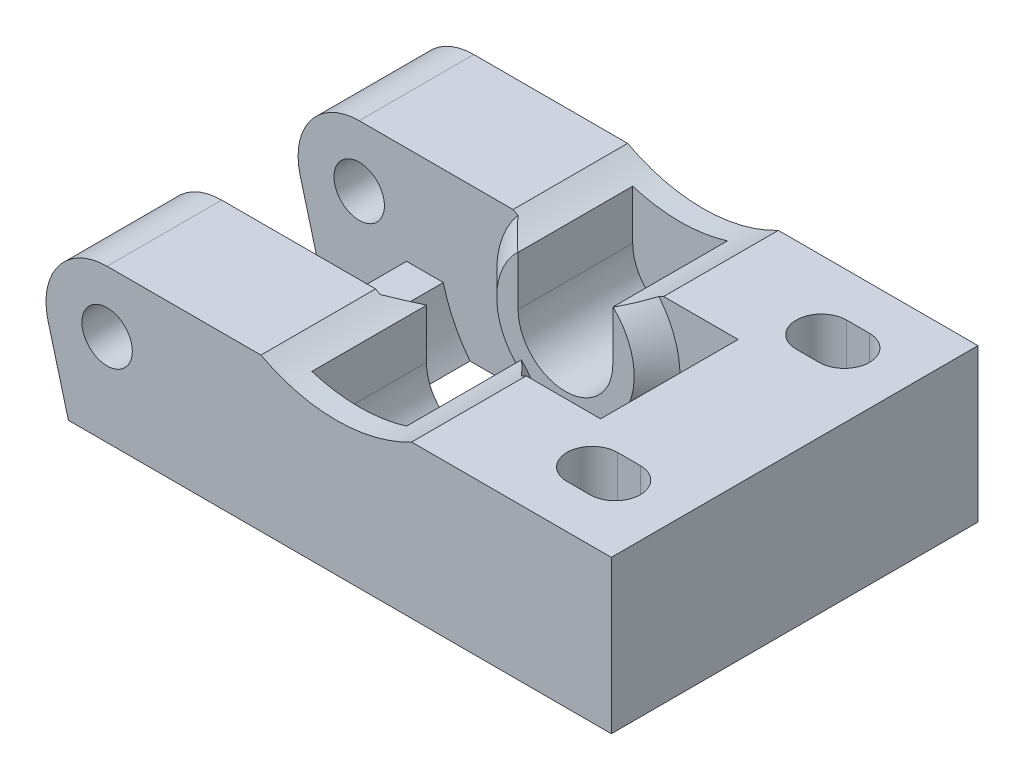
SolidWorks part; units mm, degrees
ref_plane "Front Plane" through (0, 0, 0) normal (0, 0, 1) x (1, 0, 0)
ref_plane "Top Plane" through (0, 0, 0) normal (0, 1, 0) x (1, 0, 0)
ref_plane "Right Plane" through (0, 0, 0) normal (1, 0, 0) x (0, 0, -1)
sketch "Sketch1" plane through (0, 0, 0) normal (0, 0, 1) x (1, 0, 0)
  line L0 (-18.8637, -1.0353) -> (-17.5334, -6)
  line L1 (-17.5334, -6) -> (18, -6)
  line L3 (-15, 4) -> (18, 4)
  line L4 (18, -6) -> (18, 4)
  circle A1 centre (-15, 0) radius 1.65
  arc A2 (-15, 4) -> (-18.8637, -1.0353) centre (-15, 0) ccw
  dimension "D2" = 4
  dimension "D3" = 3.3
  dimension "D4" = 4
  dimension "D1" = 15
  dimension "D5" = 10
  dimension "D6" = 105
  dimension "D7" = 18
extrude "Boss-Extrude1" add sketch "Sketch1" along normal blind 24
ref_plane "Plane1" through (0, 0, 12) normal (0, 0, 1) x (1, 0, 0)
sketch "Sketch2" plane through (0, 0, 12) normal (0, 0, 1) x (1, 0, 0)
  line L0 (-11.9012, -2.4212) -> (-19.8091, -31.934)
  line L1 (-19.8091, 9.8) -> (9.8, 9.8)
  line L2 (9.8, 9.8) -> (9.8, 0)
  line L3 (-19.8091, -31.934) -> (-19.8091, 9.8)
  line L4 (-11.9012, -2.4212) -> (-9.4962, -2.4212)
  arc A0 (-9.4962, -2.4212) -> (9.8, 0) centre (0, 0) ccw
  dimension "D1" = 19.6
  dimension "D3" = 15
extrude "Cut-Extrude1" cut sketch "Sketch2" against normal blind 4.5 and the other way blind 4.5
sketch "Sketch4" plane through (0, 0, 12) normal (0, 0, 1) x (1, 0, 0)
  line L0 (-3.1, 0) -> (-3.1, 6.453)
  line L1 (-3.1, 6.453) -> (3.1, 6.453)
  line L2 (3.1, 6.453) -> (3.1, 0)
  arc A0 (-3.1, 0) -> (3.1, 0) centre (0, 0) ccw
  dimension "D1" = 3.1
extrude "Cut-Extrude3" cut sketch "Sketch4" against normal blind 10.5 and the other way blind 10.5
ref_axis "Axis1" through (0, 0, 7.5) along (0, 0, -1)
sketch "Sketch3" plane through (0, -6, 0) normal (0, -1, 0) x (1, 0, 0)
  line L0 (13, 19.5) -> (13, 3.8848) construction
  line L1 (13.75, 19.5) -> (12.25, 19.5) construction
  line L2 (13.75, 17.85) -> (12.25, 17.85)
  line L3 (13.75, 21.15) -> (12.25, 21.15)
  line L4 (0, 7.5) -> (0, 1.5) construction
  line L5 (5.5, 12) -> (-5.5, 12) construction
  line L6 (15.943, 12) -> (0, 12) construction
  line L7 (13.75, 4.5) -> (12.25, 4.5) construction
  line L8 (13.75, 6.15) -> (12.25, 6.15)
  line L9 (13.75, 2.85) -> (12.25, 2.85)
  arc A0 (13.75, 17.85) -> (13.75, 21.15) centre (13.75, 19.5) ccw
  arc A1 (12.25, 21.15) -> (12.25, 17.85) centre (12.25, 19.5) ccw
  arc A2 (13.75, 6.15) -> (13.75, 2.85) centre (13.75, 4.5) cw
  arc A3 (12.25, 2.85) -> (12.25, 6.15) centre (12.25, 4.5) cw
  point P4 (13, 19.5)
  point P17 (13, 4.5)
  dimension "D2" = 1.65
  dimension "D1" = 1.5
  dimension "D3" = 13
  dimension "D4" = 7.5
extrude "Cut-Extrude2" cut sketch "Sketch3" against normal through all
sketch "Sketch5" plane through (0, 0, 7.5) normal (0, 0, 1) x (1, 0, 0)
  line L0 (-3.1, 0) -> (-3.1, 3.2619)
  line L1 (3.1, 0) -> (3.1, 3.2619)
  arc A0 (-3.1, 0) -> (3.1, 0) centre (0, 0) ccw
  arc A1 (-3.1, 3.2619) -> (3.1, 3.2619) centre (0, 0) ccw
  arc A2 (-3.1, 0) -> (3.1, 0) centre (0, 0) ccw construction
  dimension "D1" = 4.5
extrude "Boss-Extrude2" add sketch "Sketch5" along normal blind 1.5
sketch "Sketch6" plane through (0, 0, 16.5) normal (0, 0, -1) x (-1, 0, 0)
  line L0 (-3.1, 0) -> (-3.1, 3.2619)
  line L3 (3.1, 0) -> (3.1, 3.2619)
  arc A0 (-3.1, 0) -> (3.1, 0) centre (0, 0) ccw
  arc A1 (-3.1, 3.2619) -> (3.1, 3.2619) centre (0, 0) ccw
  arc A2 (-3.1, 0) -> (3.1, 0) centre (0, 0) ccw construction
  dimension "D1" = 4.5
extrude "Boss-Extrude3" add sketch "Sketch6" along normal blind 1.5
chamfer "Chamfer1" distance 1.5 angle 45 2 edges at (0, -4.5, 7.5) (0, -4.5, 16.5)
sketch "Sketch7" plane through (0, 0, 24) normal (0, 0, 1) x (1, 0, 0)
  line L0 (0, 0) -> (0, 13.27) construction
  circle A0 centre (0, 13.27) radius 10.5
  dimension "D2" = 21
  dimension "D1" = 13.27
extrude "Cut-Extrude4" cut sketch "Sketch7" against normal through all
